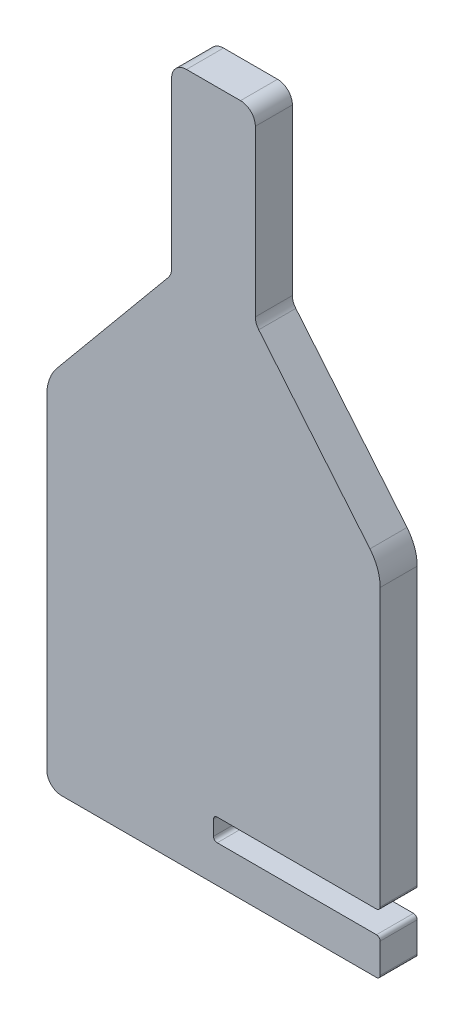
SolidWorks part; units mm, degrees
ref_plane "Alzado" through (0, 0, 0) normal (0, 0, 1) x (1, 0, 0)
ref_plane "Planta" through (0, 0, 0) normal (0, 1, 0) x (1, 0, 0)
ref_plane "Vista lateral" through (0, 0, 0) normal (1, 0, 0) x (0, 0, -1)
sketch "Croquis1" plane through (0, 0, 0) normal (0, 0, 1) x (1, 0, 0)
  line L0 (-5.65, 20) -> (-22.5, -0.3233)
  line L1 (-5.65, 45) -> (5.65, 45)
  line L2 (-22.5, -0.3233) -> (-22.5, -48.3233)
  line L3 (-22.5, -48.3233) -> (22.5, -48.3233)
  line L4 (22.5, -0.3233) -> (22.5, -48.3233)
  line L5 (-5.65, 45) -> (5.65, 45)
  line L6 (-5.65, 45) -> (-5.65, 20)
  line L8 (5.65, 45) -> (5.65, 19.9991)
  line L9 (5.65, 19.9991) -> (22.5, -0.3233)
  line L10 (0, 75.1867) -> (0, -77.6145) construction
  dimension "D1" = 45
  dimension "D2" = 25
  dimension "D3" = 5.65
  dimension "D4" = 22.5
  dimension "D5" = 45
  dimension "D6" = 5.65
  dimension "D7" = 26.3993
  dimension "D8" = 26.4
  dimension "D9" = 48
  dimension "D10" = 48
extrude "Saliente-Extruir1" add sketch "Croquis1" along normal blind 5 contours L6 L0 L2 L3 L4 L9 L8 L1
sketch "Croquis3" plane through (0, 0, 5) normal (0, 0, 1) x (1, 0, 0)
  line L0 (22.5, -0.3233) -> (22.5, -48.3233) construction
  line L1 (22.5, -40.3233) -> (0, -40.3233)
  line L2 (22.5, -40.3233) -> (22.5, -43.3233)
  line L3 (22.5, -43.3233) -> (0, -43.3233)
  line L4 (0, -40.3233) -> (0, -43.3233)
  line L5 (-22.5, -48.3233) -> (22.5, -48.3233) construction
  dimension "D1" = 3
  dimension "D2" = 5
  dimension "D3" = 22.5
extrude "Cortar-Extruir2" cut sketch "Croquis3" against normal up to surface (5 mm away) up to face at (0, 4.0882, 0)
fillet "Redondeo1" radius 2 5 edges at (-22.5, -48.3233, 2.5) (-5.65, 20, 2.5) (-5.65, 45, 2.5) (5.65, 19.9991, 2.5) (5.65, 45, 2.5)
fillet "Redondeo2" radius 6 2 edges at (-22.5, -0.3233, 2.5) (22.5, -0.3233, 2.5)
fillet "Redondeo3" radius 0.5 5 edges at (0, -40.3233, 2.5) (0, -43.3233, 2.5) (22.5, -48.3233, 2.5) (22.5, -43.3233, 2.5) (22.5, -40.3233, 2.5)
